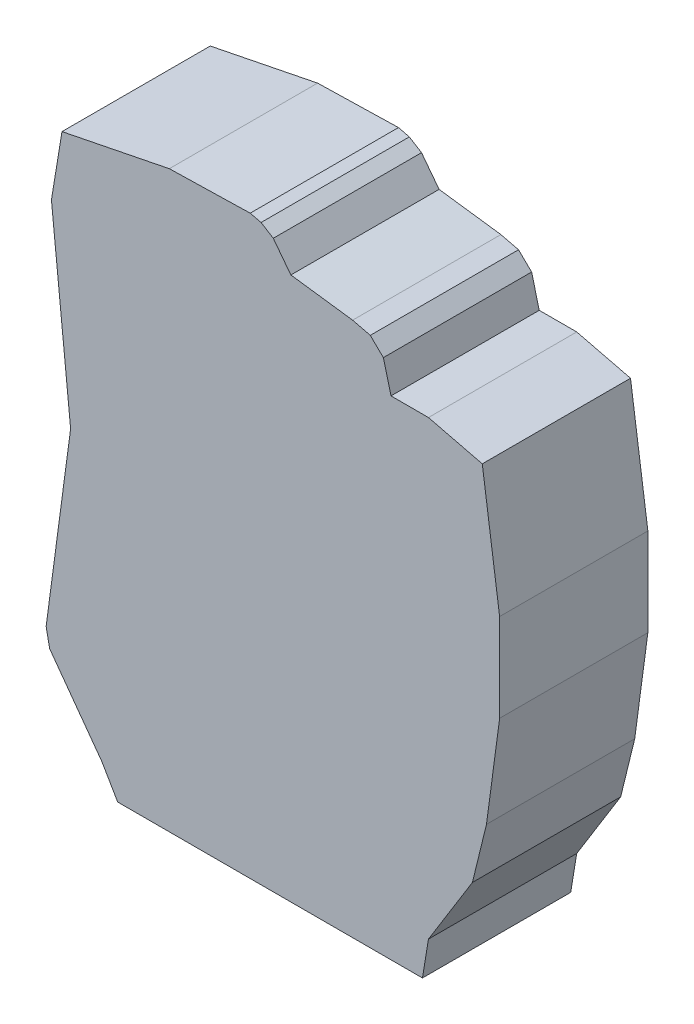
SolidWorks part; units mm, degrees
ref_plane "Front Plane" through (0, 0, 0) normal (0, 0, 1) x (1, 0, 0)
ref_plane "Top Plane" through (0, 0, 0) normal (0, 1, 0) x (1, 0, 0)
ref_plane "Right Plane" through (0, 0, 0) normal (1, 0, 0) x (0, 0, -1)
sketch "Sketch1" plane through (0, 0, 0) normal (0, 0, 1) x (1, 0, 0)
  line L0 (6.2196, 20.172) -> (31.0978, 20.172) construction
  line L16 (546.873, 9.9176) -> (893.0858, 9.9176) construction
  line L17 (543.5946, 13.7694) -> (705.2646, 13.7694) construction
  line L43 (547.2066, 9.9086) -> (608.8766, 9.9086) construction
  line L44 (546.5809, 9.8961) -> (608.2509, 9.8961)
  line L45 (608.2509, 9.8961) -> (609.4687, 17.3252)
  line L46 (609.4687, 17.3252) -> (618.3641, 31.6987)
  line L47 (618.3641, 31.6987) -> (621.2095, 43.3087)
  line L48 (621.2095, 43.3087) -> (623.8684, 63.2242)
  line L49 (623.8684, 63.2242) -> (623.8684, 81.0545)
  line L50 (623.8684, 81.0545) -> (620.3573, 106.0595)
  line L51 (620.3573, 106.0595) -> (609.4687, 108.7281)
  line L52 (609.4687, 108.7281) -> (601.8876, 108.7281)
  line L53 (601.8876, 108.7281) -> (600.3424, 114.6689)
  line L54 (600.3424, 114.6689) -> (597.6933, 117.2443)
  line L55 (597.6933, 117.2443) -> (594.1218, 118.1197)
  line L56 (594.1218, 118.1197) -> (581.6232, 119.7883)
  line L57 (581.6232, 119.7883) -> (578.0652, 124.4428)
  line L58 (578.0652, 124.4428) -> (575.593, 125.9728)
  line L59 (575.593, 125.9728) -> (573.398, 126.5107)
  line L60 (573.398, 126.5107) -> (557.03, 126.1181)
  line L61 (557.03, 126.1181) -> (535.3097, 121.7603)
  line L62 (535.3097, 121.7603) -> (533.8832, 113.0576)
  line L63 (533.8832, 113.0576) -> (533.1735, 108.7281)
  line L64 (533.1735, 108.7281) -> (536.3202, 77.7869)
  line L65 (536.3202, 77.7869) -> (537.0549, 70.5624)
  line L66 (537.0549, 70.5624) -> (532.0987, 33.4394)
  line L67 (532.0987, 33.4394) -> (532.8106, 29.8912)
  line L68 (532.8106, 29.8912) -> (543.389, 15.3737)
  line L69 (543.389, 15.3737) -> (546.5809, 9.8961)
  dimension "D1" = 61.67
  dimension "D2" = 61.67
extrude "Boss-Extrude1" add sketch "Sketch1" along normal blind 30
ref_plane "Plane1" through (530, 0, 0) normal (1, 0, 0) x (0, 0, -1)
sketch "Sketch2" plane through (530, 0, 0) normal (1, 0, 0) x (0, 0, -1)
  line L0 (-24.212, 126.5107) -> (-24.212, 90.6107)
  line L1 (-30, 126.5107) -> (0, 126.5107) construction
  line L2 (-24.212, 90.6107) -> (-30, 81.3731)
  line L3 (-30, 108.7281) -> (-30, 70.5624) construction
  line L4 (-24.212, 90.6107) -> (-24.212, 79.6081) construction
  line L5 (-24.212, 126.5107) -> (-30, 126.5107)
  line L7 (-30, 126.5107) -> (-30, 81.3731)
  dimension "D1" = 35.9
  dimension "D2" = 5.788
  dimension "D3" = 32.07
